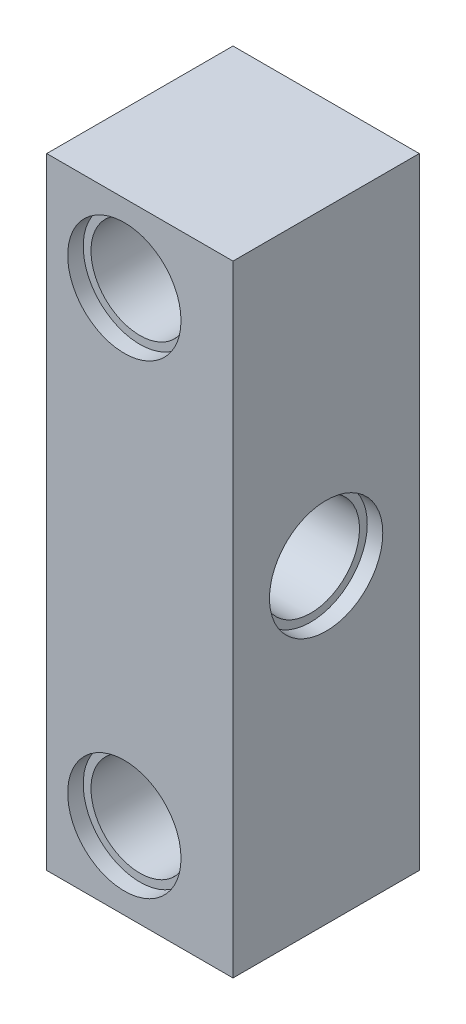
SolidWorks part; units mm, degrees
ref_plane "Front" through (0, 0, 0) normal (0, 0, 1) x (1, 0, 0)
ref_plane "Top" through (0, 0, 0) normal (0, 1, 0) x (1, 0, 0)
ref_plane "Right" through (0, 0, 0) normal (1, 0, 0) x (0, 0, -1)
sketch "Esquisse1" plane through (0, 0, 0) normal (0, 0, 1) x (1, 0, 0)
  line L1 (0, 0) -> (12, 0)
  line L2 (0, 0) -> (0, 40)
  line L3 (0, 40) -> (12, 40)
  line L4 (12, 0) -> (12, 40)
  dimension "D1" = 12
  dimension "D2" = 40
extrude "Boss.-Extru.1" add sketch "Esquisse1" along normal blind 12
sketch "Esquisse3" plane through (0, 0, 12) normal (0, 0, 1) x (1, 0, 0)
  line L0 (5, 40) -> (5, 0) construction
  line L2 (0, 0) -> (12, 0) construction
  line L3 (12, 40) -> (0, 40) construction
  line L4 (0, 40) -> (0, 0) construction
  circle A0 centre (5, 5) radius 3.15
  circle A1 centre (5, 35) radius 3.15
  dimension "D1" = 30
  dimension "D2" = 5
  dimension "D3" = 6.3
  dimension "D4" = 5
extrude "Enlèv. mat.-Extru.1" cut sketch "Esquisse3" against normal through all both and the other way through all
sketch "Esquisse4" plane through (12, 0, 0) normal (1, 0, 0) x (0, 0, -1)
  line L0 (-6, 0) -> (-6, 40) construction
  line L1 (-12, 0) -> (0, 0) construction
  line L2 (-12, 40) -> (0, 40) construction
  circle A0 centre (-6, 20) radius 3.15
  dimension "D1" = 6.3
extrude "Enlèv. mat.-Extru.2" cut sketch "Esquisse4" against normal through all both and the other way through all
sketch "Esquisse5" plane through (0, 0, 12) normal (0, 0, 1) x (1, 0, 0)
  circle A0 centre (5, 35) radius 3.65
  circle A1 centre (5, 5) radius 3.65
  dimension "D1" = 7.3
extrude "Enlèv. mat.-Extru.3" cut sketch "Esquisse5" against normal blind 1
sketch "Esquisse6" plane through (12, 0, 0) normal (1, 0, 0) x (0, 0, -1)
  circle A0 centre (-6, 20) radius 3.65
  dimension "D1" = 7.3
extrude "Enlèv. mat.-Extru.4" cut sketch "Esquisse6" against normal blind 1
